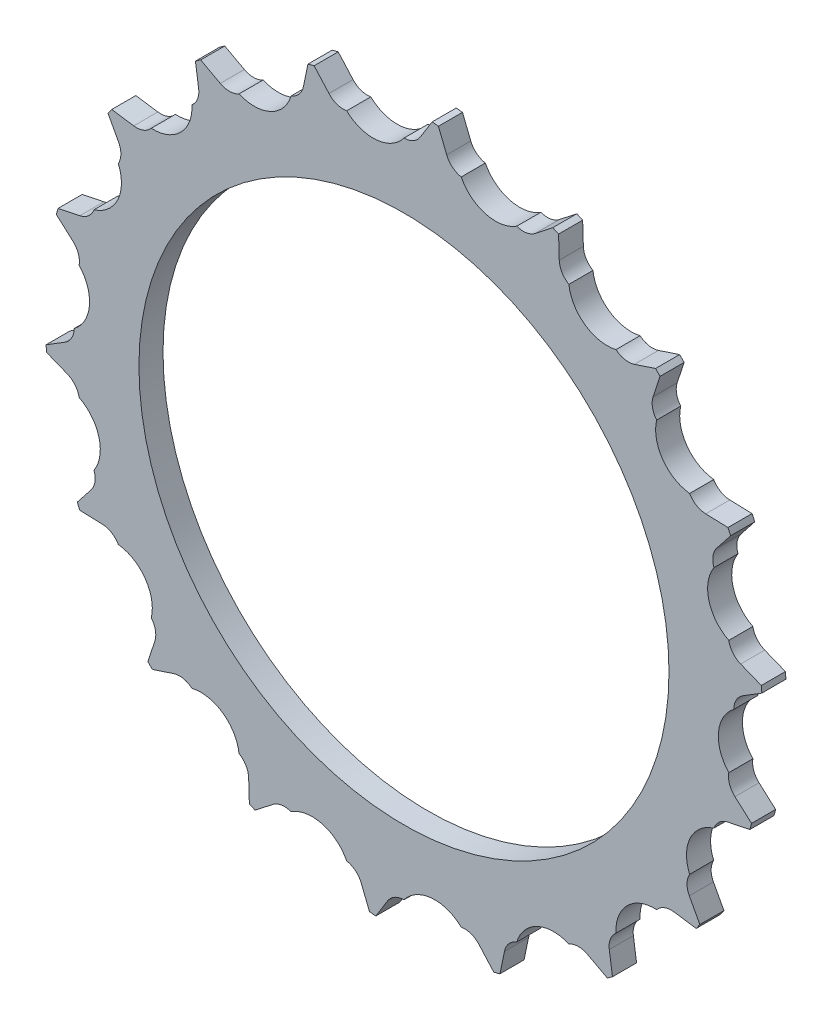
SolidWorks part; units mm, degrees
ref_plane "Front Plane" through (0, 0, 0) normal (0, 0, 1) x (1, 0, 0)
ref_plane "Top Plane" through (0, 0, 0) normal (0, 1, 0) x (1, 0, 0)
ref_plane "Right Plane" through (0, 0, 0) normal (1, 0, 0) x (0, 0, -1)
sketch "Sketch1" plane through (0, 0, 0) normal (0, 0, 1) x (1, 0, 0)
  line L0 (3.4006, 70.3439) -> (6.0855, 74.679)
  line L1 (3.4006, 70.3439) -> (8.8661, 69.8657) construction
  line L2 (6.9749, 74.6012) -> (8.8661, 69.8657)
  line L3 (3.4006, 70.3439) -> (0, 0) construction
  line L4 (0, 0) -> (8.8661, 69.8657) construction
  line L5 (15.5641, 68.6847) -> (18.9609, 72.4877)
  line L6 (19.8233, 72.2567) -> (20.8635, 67.2647)
  line L7 (27.2546, 64.9386) -> (31.2602, 68.094)
  line L8 (32.0693, 67.7166) -> (32.2269, 62.6199)
  line L9 (38.117, 59.2193) -> (42.6097, 61.6312)
  line L10 (43.341, 61.1191) -> (42.6111, 56.0725)
  line L11 (47.8212, 51.7007) -> (52.6645, 53.2958)
  line L12 (53.2958, 52.6645) -> (51.7007, 47.8212)
  line L13 (56.0725, 42.6111) -> (61.1191, 43.341)
  line L14 (61.6312, 42.6097) -> (59.2193, 38.117)
  line L15 (62.6199, 32.2269) -> (67.7166, 32.0693)
  line L16 (68.094, 31.2602) -> (64.9386, 27.2546)
  line L17 (67.2647, 20.8635) -> (72.2567, 19.8233)
  line L18 (72.4877, 18.9609) -> (68.6847, 15.5641)
  line L19 (69.8657, 8.8661) -> (74.6012, 6.9749)
  line L20 (74.679, 6.0855) -> (70.3439, 3.4006)
  line L21 (70.3439, -3.4006) -> (74.679, -6.0855)
  line L22 (74.6012, -6.9749) -> (69.8657, -8.8661)
  line L23 (68.6847, -15.5641) -> (72.4877, -18.9609)
  line L24 (72.2567, -19.8233) -> (67.2647, -20.8635)
  line L25 (64.9386, -27.2546) -> (68.094, -31.2602)
  line L26 (67.7166, -32.0693) -> (62.6199, -32.2269)
  line L27 (59.2193, -38.117) -> (61.6312, -42.6097)
  line L28 (61.1191, -43.341) -> (56.0725, -42.6111)
  line L29 (51.7007, -47.8212) -> (53.2958, -52.6645)
  line L30 (52.6645, -53.2958) -> (47.8212, -51.7007)
  line L31 (42.6111, -56.0725) -> (43.341, -61.1191)
  line L32 (42.6097, -61.6312) -> (38.117, -59.2193)
  line L33 (32.2269, -62.6199) -> (32.0693, -67.7166)
  line L34 (31.2602, -68.094) -> (27.2546, -64.9386)
  line L35 (20.8635, -67.2647) -> (19.8233, -72.2567)
  line L36 (18.9609, -72.4877) -> (15.5641, -68.6847)
  line L37 (8.8661, -69.8657) -> (6.9749, -74.6012)
  line L38 (6.0855, -74.679) -> (3.4006, -70.3439)
  line L39 (-3.4006, -70.3439) -> (-6.0855, -74.679)
  line L40 (-6.9749, -74.6012) -> (-8.8661, -69.8657)
  line L41 (-15.5641, -68.6847) -> (-18.9609, -72.4877)
  line L42 (-19.8233, -72.2567) -> (-20.8635, -67.2647)
  line L43 (-27.2546, -64.9386) -> (-31.2602, -68.094)
  line L44 (-32.0693, -67.7166) -> (-32.2269, -62.6199)
  line L45 (-38.117, -59.2193) -> (-42.6097, -61.6312)
  line L46 (-43.341, -61.1191) -> (-42.6111, -56.0725)
  line L47 (-47.8212, -51.7007) -> (-52.6645, -53.2958)
  line L48 (-53.2958, -52.6645) -> (-51.7007, -47.8212)
  line L49 (-56.0725, -42.6111) -> (-61.1191, -43.341)
  line L50 (-61.6312, -42.6097) -> (-59.2193, -38.117)
  line L51 (-62.6199, -32.2269) -> (-67.7166, -32.0693)
  line L52 (-68.094, -31.2602) -> (-64.9386, -27.2546)
  line L53 (-67.2647, -20.8635) -> (-72.2567, -19.8233)
  line L54 (-72.4877, -18.9609) -> (-68.6847, -15.5641)
  line L55 (-69.8657, -8.8661) -> (-74.6012, -6.9749)
  line L56 (-74.679, -6.0855) -> (-70.3439, -3.4006)
  line L57 (-70.3439, 3.4006) -> (-74.679, 6.0855)
  line L58 (-74.6012, 6.9749) -> (-69.8657, 8.8661)
  line L59 (-68.6847, 15.5641) -> (-72.4877, 18.9609)
  line L60 (-72.2567, 19.8233) -> (-67.2647, 20.8635)
  line L61 (-64.9386, 27.2546) -> (-68.094, 31.2602)
  line L62 (-67.7166, 32.0693) -> (-62.6199, 32.2269)
  line L63 (-59.2193, 38.117) -> (-61.6312, 42.6097)
  line L64 (-61.1191, 43.341) -> (-56.0725, 42.6111)
  line L65 (-51.7007, 47.8212) -> (-53.2958, 52.6645)
  line L66 (-52.6645, 53.2958) -> (-47.8212, 51.7007)
  line L67 (-42.6111, 56.0725) -> (-43.341, 61.1191)
  line L68 (-42.6097, 61.6312) -> (-38.117, 59.2193)
  line L69 (-32.2269, 62.6199) -> (-32.0693, 67.7166)
  line L70 (-31.2602, 68.094) -> (-27.2546, 64.9386)
  line L71 (-20.8635, 67.2647) -> (-19.8233, 72.2567)
  line L72 (-18.9609, 72.4877) -> (-15.5641, 68.6847)
  line L73 (-8.8661, 69.8657) -> (-6.9749, 74.6012)
  line L74 (-6.0855, 74.679) -> (-3.4006, 70.3439)
  line L83 (0, 72.45) -> (0, 0) construction
  line L84 (0, 0) -> (6.5105, 74.4157) construction
  circle A0 centre (0, 0) radius 72.45 construction
  arc A1 (-3.9985, 72.3396) -> (3.4006, 70.3439) centre (0, 72.45) ccw
  arc A2 (4.6139, 72.3029) -> (8.0115, 72.0057) centre (0, 0) cw
  arc A3 (6.0855, 74.679) -> (6.9749, 74.6012) centre (6.5105, 74.4157) cw
  arc A4 (8.6239, 71.9349) -> (15.5641, 68.6847) centre (12.5808, 71.3493) ccw
  arc A5 (18.9609, 72.4877) -> (19.8233, 72.2567) centre (19.3338, 72.1547) cw
  arc A6 (20.9843, 69.3445) -> (27.2546, 64.9386) centre (24.7794, 68.0807) ccw
  arc A7 (31.2602, 68.094) -> (32.0693, 67.7166) centre (31.5696, 67.7012) cw
  arc A8 (32.707, 64.6472) -> (38.117, 59.2193) centre (36.225, 62.7435) ccw
  arc A9 (42.6097, 61.6312) -> (43.341, 61.1191) centre (42.8462, 61.1907) cw
  arc A10 (43.436, 57.9855) -> (47.8212, 51.7007) centre (46.57, 55.4999) ccw
  arc A11 (52.6645, 53.2958) -> (53.2958, 52.6645) centre (52.8209, 52.8209) cw
  arc A12 (52.8452, 49.562) -> (56.0725, 42.6111) centre (55.4999, 46.57) ccw
  arc A13 (61.1191, 43.341) -> (61.6312, 42.6097) centre (61.1907, 42.8462) cw
  arc A14 (60.6487, 39.6326) -> (62.6199, 32.2269) centre (62.7435, 36.225) ccw
  arc A15 (67.7166, 32.0693) -> (68.094, 31.2602) centre (67.7012, 31.5696) cw
  arc A16 (66.6094, 28.4989) -> (67.2647, 20.8635) centre (68.0807, 24.7794) ccw
  arc A17 (72.2567, 19.8233) -> (72.4877, 18.9609) centre (72.1547, 19.3338) cw
  arc A18 (70.5463, 16.4994) -> (69.8657, 8.8661) centre (71.3493, 12.5808) ccw
  arc A19 (74.6012, 6.9749) -> (74.679, 6.0855) centre (74.4157, 6.5105) cw
  arc A20 (72.3396, 3.9985) -> (70.3439, -3.4006) centre (72.45, 0) ccw
  arc A21 (74.679, -6.0855) -> (74.6012, -6.9749) centre (74.4157, -6.5105) cw
  arc A22 (71.9349, -8.6239) -> (68.6847, -15.5641) centre (71.3493, -12.5808) ccw
  arc A23 (72.4877, -18.9609) -> (72.2567, -19.8233) centre (72.1547, -19.3338) cw
  arc A24 (69.3445, -20.9843) -> (64.9386, -27.2546) centre (68.0807, -24.7794) ccw
  arc A25 (68.094, -31.2602) -> (67.7166, -32.0693) centre (67.7012, -31.5696) cw
  arc A26 (64.6472, -32.707) -> (59.2193, -38.117) centre (62.7435, -36.225) ccw
  arc A27 (61.6312, -42.6097) -> (61.1191, -43.341) centre (61.1907, -42.8462) cw
  arc A28 (57.9855, -43.436) -> (51.7007, -47.8212) centre (55.4999, -46.57) ccw
  arc A29 (53.2958, -52.6645) -> (52.6645, -53.2958) centre (52.8209, -52.8209) cw
  arc A30 (49.562, -52.8452) -> (42.6111, -56.0725) centre (46.57, -55.4999) ccw
  arc A31 (43.341, -61.1191) -> (42.6097, -61.6312) centre (42.8462, -61.1907) cw
  arc A32 (39.6326, -60.6487) -> (32.2269, -62.6199) centre (36.225, -62.7435) ccw
  arc A33 (32.0693, -67.7166) -> (31.2602, -68.094) centre (31.5696, -67.7012) cw
  arc A34 (28.4989, -66.6094) -> (20.8635, -67.2647) centre (24.7794, -68.0807) ccw
  arc A35 (19.8233, -72.2567) -> (18.9609, -72.4877) centre (19.3338, -72.1547) cw
  arc A36 (16.4994, -70.5463) -> (8.8661, -69.8657) centre (12.5808, -71.3493) ccw
  arc A37 (6.9749, -74.6012) -> (6.0855, -74.679) centre (6.5105, -74.4157) cw
  arc A38 (3.9985, -72.3396) -> (-3.4006, -70.3439) centre (0, -72.45) ccw
  arc A39 (-6.0855, -74.679) -> (-6.9749, -74.6012) centre (-6.5105, -74.4157) cw
  arc A40 (-8.6239, -71.9349) -> (-15.5641, -68.6847) centre (-12.5808, -71.3493) ccw
  arc A41 (-18.9609, -72.4877) -> (-19.8233, -72.2567) centre (-19.3338, -72.1547) cw
  arc A42 (-20.9843, -69.3445) -> (-27.2546, -64.9386) centre (-24.7794, -68.0807) ccw
  arc A43 (-31.2602, -68.094) -> (-32.0693, -67.7166) centre (-31.5696, -67.7012) cw
  arc A44 (-32.707, -64.6472) -> (-38.117, -59.2193) centre (-36.225, -62.7435) ccw
  arc A45 (-42.6097, -61.6312) -> (-43.341, -61.1191) centre (-42.8462, -61.1907) cw
  arc A46 (-43.436, -57.9855) -> (-47.8212, -51.7007) centre (-46.57, -55.4999) ccw
  arc A47 (-52.6645, -53.2958) -> (-53.2958, -52.6645) centre (-52.8209, -52.8209) cw
  arc A48 (-52.8452, -49.562) -> (-56.0725, -42.6111) centre (-55.4999, -46.57) ccw
  arc A49 (-61.1191, -43.341) -> (-61.6312, -42.6097) centre (-61.1907, -42.8462) cw
  arc A50 (-60.6487, -39.6326) -> (-62.6199, -32.2269) centre (-62.7435, -36.225) ccw
  arc A51 (-67.7166, -32.0693) -> (-68.094, -31.2602) centre (-67.7012, -31.5696) cw
  arc A52 (-66.6094, -28.4989) -> (-67.2647, -20.8635) centre (-68.0807, -24.7794) ccw
  arc A53 (-72.2567, -19.8233) -> (-72.4877, -18.9609) centre (-72.1547, -19.3338) cw
  arc A54 (-70.5463, -16.4994) -> (-69.8657, -8.8661) centre (-71.3493, -12.5808) ccw
  arc A55 (-74.6012, -6.9749) -> (-74.679, -6.0855) centre (-74.4157, -6.5105) cw
  arc A56 (-72.3396, -3.9985) -> (-70.3439, 3.4006) centre (-72.45, 0) ccw
  arc A57 (-74.679, 6.0855) -> (-74.6012, 6.9749) centre (-74.4157, 6.5105) cw
  arc A58 (-71.9349, 8.6239) -> (-68.6847, 15.5641) centre (-71.3493, 12.5808) ccw
  arc A59 (-72.4877, 18.9609) -> (-72.2567, 19.8233) centre (-72.1547, 19.3338) cw
  arc A60 (-69.3445, 20.9843) -> (-64.9386, 27.2546) centre (-68.0807, 24.7794) ccw
  arc A61 (-68.094, 31.2602) -> (-67.7166, 32.0693) centre (-67.7012, 31.5696) cw
  arc A62 (-64.6472, 32.707) -> (-59.2193, 38.117) centre (-62.7435, 36.225) ccw
  arc A63 (-61.6312, 42.6097) -> (-61.1191, 43.341) centre (-61.1907, 42.8462) cw
  arc A64 (-57.9855, 43.436) -> (-51.7007, 47.8212) centre (-55.4999, 46.57) ccw
  arc A65 (-53.2958, 52.6645) -> (-52.6645, 53.2958) centre (-52.8209, 52.8209) cw
  arc A66 (-49.562, 52.8452) -> (-42.6111, 56.0725) centre (-46.57, 55.4999) ccw
  arc A67 (-43.341, 61.1191) -> (-42.6097, 61.6312) centre (-42.8462, 61.1907) cw
  arc A68 (-39.6326, 60.6487) -> (-32.2269, 62.6199) centre (-36.225, 62.7435) ccw
  arc A69 (-32.0693, 67.7166) -> (-31.2602, 68.094) centre (-31.5696, 67.7012) cw
  arc A70 (-28.4989, 66.6094) -> (-20.8635, 67.2647) centre (-24.7794, 68.0807) ccw
  arc A71 (-19.8233, 72.2567) -> (-18.9609, 72.4877) centre (-19.3338, 72.1547) cw
  arc A72 (-16.4994, 70.5463) -> (-8.8661, 69.8657) centre (-12.5808, 71.3493) ccw
  arc A73 (-6.9749, 74.6012) -> (-6.0855, 74.679) centre (-6.5105, 74.4157) cw
  point P289 (0, 0)
  dimension "D1" = 144.9
  dimension "D2" = 4
  dimension "D5" = 0.5
  dimension "D6" = 74.7
  dimension "D3" = 5
  dimension "D4" = 36
extrude "Boss-Extrude1" add sketch "Sketch1" along normal blind 5 contours L74 A73 L73 A72 L72 A71 L71 A70 L70 A69 L69 A68 L68 A67 L67 A66 L66 A65 L65 A64 L64 A63 L63 A62 L62 A61 L61 A60 L60 A59 L59 A58 L58 A57 L57 A56 | A3 L0 A2 L2 region at (-0.0022, -0.0255, 0) region at (6.4054, 73.214, 0)
sketch "Sketch2" plane through (0, 0, 5) normal (0, 0, 1) x (1, 0, 0)
  circle A0 centre (0, 0) radius 12.5
  dimension "D1" = 25
extrude "Boss-Extrude2" add sketch "Sketch2" along normal blind 40
sketch "Sketch5" plane through (0, 0, 0) normal (0, 0, -1) x (-1, 0, 0)
  line L1 (0, 68.45) -> (0.611, 75.4338)
  line L2 (11.8862, 67.4101) -> (12.4972, 74.3939)
  line L3 (0.611, 75.4338) -> (12.4972, 74.3939)
  arc A0 (0, 68.45) -> (11.8862, 67.4101) centre (6.4077, 73.2398) ccw
  arc A3 (-3.4006, 70.3439) -> (3.4006, 70.3439) centre (0, 72.45) ccw construction
  arc A5 (-3.4006, 70.3439) -> (3.4006, 70.3439) centre (0, 72.45) ccw construction
  arc A7 (8.8661, 69.8657) -> (15.5641, 68.6847) centre (12.5808, 71.3493) ccw construction
  arc A8 (6.9749, 74.6012) -> (6.0855, 74.679) centre (6.5105, 74.4157) ccw construction
  point P0 (0.4708, 75.3302)
  point P8 (3, 68.45)
  point P9 (0, 0)
  point P12 (12.4972, 67.0634)
  point P15 (0.611, 68.4969)
  point P19 (0, 68.45)
  point P22 (11.8862, 67.4101)
  dimension "D4" = 8
extrude "Cut-Extrude2" cut sketch "Sketch5" against normal blind 10
sketch "Sketch9" plane through (0, 0, 0) normal (0, 0, -1) x (-1, 0, 0)
  circle A0 centre (0, 0) radius 74.5
  circle A1 centre (0, 0) radius 100
  dimension "D1" = 149
  dimension "D2" = 200
extrude "Cut-Extrude5" cut sketch "Sketch9" against normal blind 10
fillet "Fillet1" radius 30 1 edges at (12.5, 0, 5)
sketch "Sketch3" plane through (0, 0, 45) normal (0, 0, 1) x (1, 0, 0)
  circle A0 centre (0, 0) radius 5
  dimension "D1" = 10
extrude "Cut-Extrude1" cut sketch "Sketch3" against normal through all
hole_wizard "Ø1.0mm Dowel Hole1" positions "3DSketch1" profile "Sketch4" hole size "Ø1.0" standard "ANSI Metric"
sketch3d "3DSketch1"
  point P0 (-6.8176, -10.4771, 42.0201)
  point P2 (-11.0684, 5.8086, 41.6583)
sketch "Sketch4" plane through (-6.8176, -10.4771, 42.0201) normal (0, 0, 1) x (0.8382, -0.5454, 0)
  line L0 (0, 0) -> (0, 34)
  line L1 (0, 34) -> (1.4, 33.1588)
  line L2 (1.4, 33.1588) -> (1.4, 0)
  line L5 (1.4, 0) -> (0, 0)
  line L10 (0, 34) -> (-1.4, 33.1588) construction
  line L11 (0, -6.35) -> (0, 107.95) construction
  dimension "Hole Dia." = 2.8
  dimension "Hole Depth" = 34
  dimension "Drill Angle" = 118
pattern_circular "CirPattern1" count 18 over 360 about axis through (0, 0, 0) along (0, 0, 1) of "Cut-Extrude2"
sketch "Sketch6" plane through (0, 0, 0) normal (0, 1, 0) x (1, 0, 0)
  line L1 (-74.2713, -7.3) -> (79.9055, -7.3)
  line L2 (-74.2713, -7.3) -> (-74.2713, -52.0573)
  line L3 (-74.2713, -52.0573) -> (79.9055, -52.0573)
  line L4 (79.9055, -7.3) -> (79.9055, -52.0573)
extrude "Cut-Extrude3" cut sketch "Sketch6" against normal through all both and the other way through all
sketch "Sketch7" plane through (0, 0, 0) normal (0, 0, -1) x (-1, 0, 0)
  line L1 (12.6, -7.2746) -> (12.6, 7.2746)
  line L2 (12.6, 7.2746) -> (0, 14.5492)
  line L3 (0, 14.5492) -> (-12.6, 7.2746)
  line L4 (-12.6, 7.2746) -> (-12.6, -7.2746)
  line L5 (-12.6, -7.2746) -> (0, -14.5492)
  line L6 (0, -14.5492) -> (12.6, -7.2746)
  circle A0 centre (0, 0) radius 12.6 construction
  dimension "D1" = 25.2
extrude "Cut-Extrude4" cut sketch "Sketch7" against normal through all both
sketch "Sketch10" plane through (0, 0, 0) normal (0, 0, -1) x (-1, 0, 0)
  circle A0 centre (0, 0) radius 55
  dimension "D1" = 110
extrude "Cut-Extrude6" cut sketch "Sketch10" against normal blind 10
equation "\"Teeth\"= 36"
equation "\"D4@Sketch1\"=\"Teeth\""
equation "\"D6@Sketch1\"=83/40*\"Teeth\""
equation "\"D1@Sketch1\"=161/40*\"Teeth\""
equation "\"D3@Sketch1\"=4.5/\"Teeth\"*40"
equation "\"D1@CirPattern1\"=\"Teeth\"/2"
